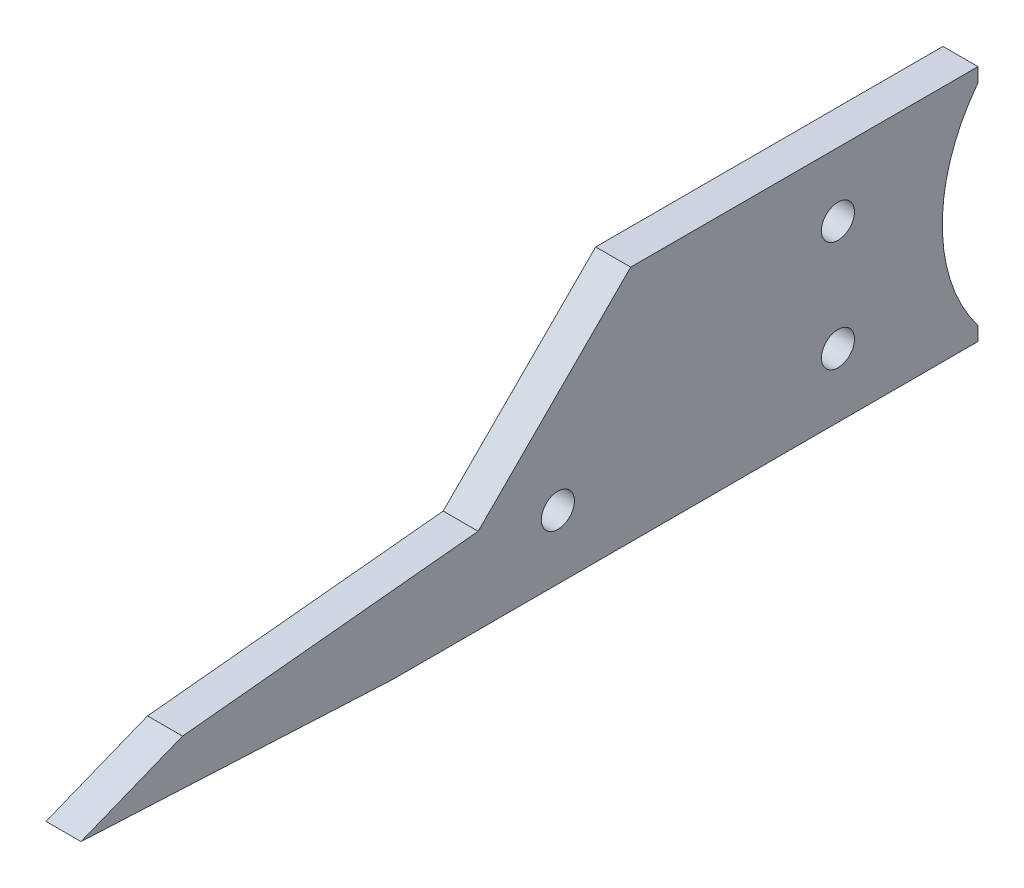
SolidWorks part; units mm, degrees
material "PE High Density"
ref_plane "Front Plane" through (0, 0, 0) normal (0, 0, 1) x (1, 0, 0)
ref_plane "Top Plane" through (0, 0, 0) normal (0, 1, 0) x (1, 0, 0)
ref_plane "Right Plane" through (0, 0, 0) normal (1, 0, 0) x (0, 0, -1)
sketch "Sketch1" plane through (0, 0, 0) normal (1, 0, 0) x (0, 0, -1)
  line L0 (-106.172, 0) -> (-62.992, 43.18)
  line L1 (0, 0) -> (-106.172, 0)
  line L2 (0, 0) -> (0, 2.54)
  line L3 (0, 43.18) -> (-62.992, 43.18)
  line L5 (0, 40.64) -> (-65.532, 40.64) construction
  line L6 (0, 2.54) -> (-103.632, 2.54) construction
  line L7 (0, 40.64) -> (0, 43.18)
  arc A0 (0, 40.64) -> (0, 2.54) centre (24.7621, 21.59) ccw
  dimension "D4" = 62.484
  dimension "D1" = 43.18
  dimension "D2" = 106.172
  dimension "D3" = 45
  dimension "D5" = 2.54
  dimension "D6" = 2.54
extrude "Boss-Extrude1" add sketch "Sketch1" along normal blind 6.35
sketch "Sketch2" plane through (6.35, 0, 0) normal (1, 0, 0) x (0, 0, -1)
  line L0 (-106.172, 0) -> (0, 0) construction
  line L1 (-68.072, 0) -> (-169.672, 0)
  line L2 (-169.672, 0) -> (-144.272, 10.16)
  line L3 (-144.272, 10.16) -> (-68.072, 17.78)
  line L4 (-68.072, 17.78) -> (-68.072, 0)
  dimension "D1" = 17.78
  dimension "D2" = 25.4
  dimension "D3" = 10.16
  dimension "D4" = 38.1
  dimension "D5" = 76.2
extrude "Boss-Extrude2" add sketch "Sketch2" against normal up to surface (6.35 mm away) up to face at (0, 21.59, 29.274)
sketch "Sketch3" plane through (6.35, 0, 0) normal (1, 0, 0) x (0, 0, -1)
  line L0 (-90.6498, 15.5222) -> (-106.172, 0) construction
  line L1 (-62.992, 43.18) -> (-90.6498, 15.5222) construction
  line L2 (-169.672, 0) -> (0, 0) construction
  line L3 (-106.172, 0) -> (-162.687, 2.794)
  line L4 (-144.272, 10.16) -> (-169.672, 0) construction
  line L5 (-162.687, 2.794) -> (-169.672, 0)
  line L6 (-169.672, 0) -> (-106.172, 0)
  dimension "D1" = 2.794
extrude "Cut-Extrude1" cut sketch "Sketch3" against normal through all
sketch "Sketch4" plane through (6.35, 0, 0) normal (1, 0, 0) x (0, 0, -1)
  line L1 (0, 0) -> (0, 2.54) construction
  line L2 (-25.4, 31.59) -> (-25.4, 11.59) construction
  circle A0 centre (-25.4, 31.59) radius 3
  circle A1 centre (-25.4, 11.59) radius 3
  arc A3 (0, 40.64) -> (0, 2.54) centre (24.7621, 21.59) ccw construction
  circle A4 centre (-76.2, 11.59) radius 3
  point P11 (-6.4799, 21.59)
  point P12 (-25.4, 21.59)
  dimension "D1" = 6
  dimension "D2" = 20
  dimension "D3" = 50.8
  dimension "D4" = 25.4
extrude "Cut-Extrude2" cut sketch "Sketch4" against normal through all
